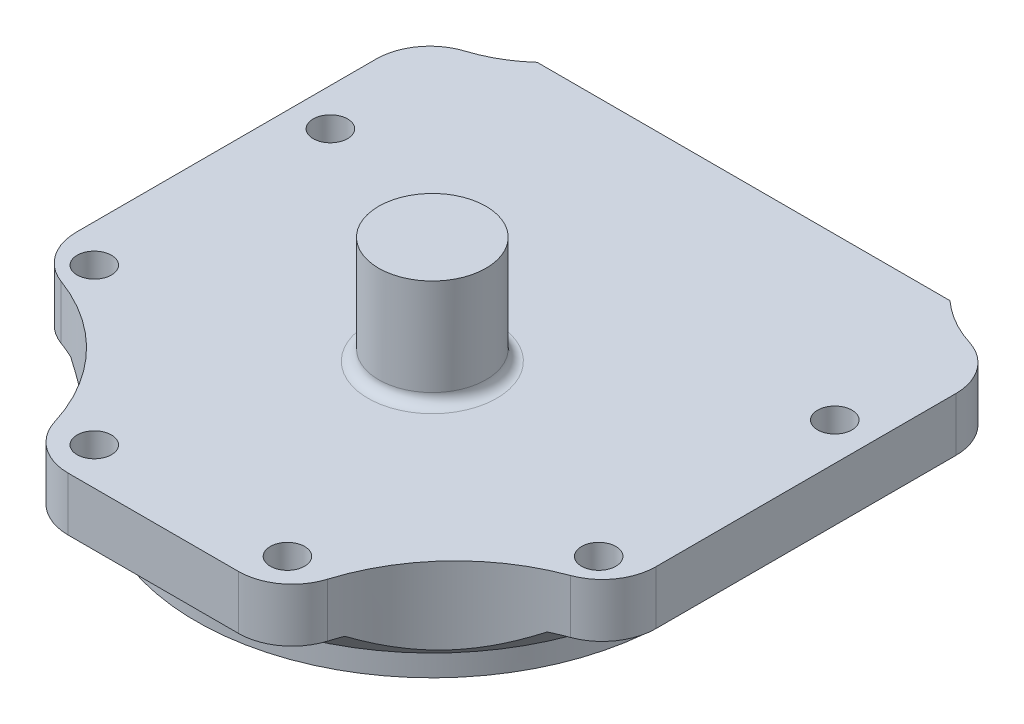
SolidWorks part; units mm, degrees
material "Резина"
ref_plane "Спереди" through (0, 0, 0) normal (0, 0, 1) x (1, 0, 0)
ref_plane "Сверху" through (0, 0, 0) normal (0, 1, 0) x (1, 0, 0)
ref_plane "Справа" through (0, 0, 0) normal (1, 0, 0) x (0, 0, -1)
ref_plane "Плоскость4" through (0, 0, 0) normal (0, -1, 0) x (-1, 0, 0)
sketch "Эскиз1" plane through (0, 0, 0) normal (0, -1, 0) x (-1, 0, 0)
  line L4 (11, -40.1669) -> (11, -12.2273)
  line L5 (3.2299, -5) -> (-35.2299, -5)
  line L6 (-43, -12.2273) -> (-43, -40.1669)
  line L7 (-23.9302, -60) -> (-8.0698, -60)
  line L8 (11, -40.1669) -> (11, -12.2273)
  line L9 (3.2299, -5) -> (-35.2299, -5)
  line L10 (-43, -12.2273) -> (-43, -40.1669)
  line L11 (-23.9302, -60) -> (-8.0698, -60)
  circle A0 centre (-39.5, -42) radius 1.6 construction
  circle A1 centre (-39.5, -20) radius 1.6 construction
  circle A3 centre (7.5, -42) radius 1.6 construction
  circle A4 centre (7.5, -20) radius 1.6 construction
  circle A5 centre (-39.5, -42) radius 1.6
  circle A6 centre (-39.5, -20) radius 1.6
  circle A7 centre (-25, -56.5) radius 1.6 construction
  circle A8 centre (7.5, -42) radius 1.6
  circle A9 centre (7.5, -20) radius 1.6
  arc A10 (11, -12.2273) -> (7.5094, -7.4605) centre (6, -12.2273) ccw
  arc A11 (3.2299, -5) -> (7.5094, -7.4605) centre (11, 3.5625) ccw
  arc A12 (-39.5094, -7.4605) -> (-35.2299, -5) centre (-43, 3.5625) ccw
  arc A13 (-39.5094, -7.4605) -> (-43, -12.2273) centre (-38, -12.2273) ccw
  arc A14 (-43, -40.1669) -> (-39.7203, -44.8616) centre (-38, -40.1669) ccw
  arc A15 (-28.7091, -56.4701) -> (-39.7203, -44.8616) centre (-45.9135, -61.7626) ccw
  arc A16 (-28.7091, -56.4701) -> (-23.9302, -60) centre (-23.9302, -55) ccw
  arc A17 (-8.0698, -60) -> (-3.2909, -56.4701) centre (-8.0698, -55) ccw
  arc A18 (7.7203, -44.8616) -> (-3.2909, -56.4701) centre (13.9135, -61.7626) ccw
  arc A19 (7.7203, -44.8616) -> (11, -40.1669) centre (6, -40.1669) ccw
  arc A20 (11, -12.2273) -> (7.5094, -7.4605) centre (6, -12.2273) ccw
  arc A21 (3.2299, -5) -> (7.5094, -7.4605) centre (11, 3.5625) ccw
  arc A22 (-39.5094, -7.4605) -> (-35.2299, -5) centre (-43, 3.5625) ccw
  arc A23 (-39.5094, -7.4605) -> (-43, -12.2273) centre (-38, -12.2273) ccw
  arc A24 (-43, -40.1669) -> (-39.7203, -44.8616) centre (-38, -40.1669) ccw
  arc A25 (-28.7091, -56.4701) -> (-39.7203, -44.8616) centre (-45.9135, -61.7626) ccw
  arc A26 (-28.7091, -56.4701) -> (-23.9302, -60) centre (-23.9302, -55) ccw
  arc A27 (-8.0698, -60) -> (-3.2909, -56.4701) centre (-8.0698, -55) ccw
  arc A28 (7.7203, -44.8616) -> (-3.2909, -56.4701) centre (13.9135, -61.7626) ccw
  arc A29 (7.7203, -44.8616) -> (11, -40.1669) centre (6, -40.1669) ccw
  circle A53 centre (-25, -56.5) radius 1.6
  circle A54 centre (-7, -56.5) radius 1.6 construction
  circle A55 centre (-7, -56.5) radius 1.6
  dimension "D1" = 0
extrude "Бобышка-Вытянуть1" add sketch "Эскиз1" along normal blind 5
sketch "Эскиз2" plane through (0, 0, 0) normal (0, 1, 0) x (1, 0, 0)
  circle A0 centre (16, -34) radius 5 construction
  circle A1 centre (16, -34) radius 5
extrude "Бобышка-Вытянуть2" add sketch "Эскиз2" along normal blind 10
fillet "Скругление1" radius 1 1 edges at (16, 0, 29)
sketch "Эскиз3" plane through (0, -5, 0) normal (0, -1, 0) x (1, 0, 0)
  circle A0 centre (16, 34) radius 5 construction
  circle A1 centre (16, 34) radius 5 construction
  circle A4 centre (16, 34) radius 22
  dimension "D2" = 44
extrude "Бобышка-Вытянуть3" add sketch "Эскиз3" along normal blind 5 contours A4
sketch "Эскиз4" plane through (0, -10, 0) normal (0, -1, 0) x (1, 0, 0)
  circle A0 centre (16, 34) radius 22 construction
  circle A1 centre (16, 34) radius 22 construction
  circle A2 centre (16, 34) radius 14
  circle A3 centre (16, 34) radius 19
  dimension "D1" = 28
  dimension "D2" = 38
extrude "Вырез-Вытянуть1" cut sketch "Эскиз4" against normal blind 7
sketch "Эскиз5" plane through (0, 0, 5) normal (0, 0, -1) x (-1, 0, 0)
  line L0 (-16, 0) -> (-16, -5) construction
  line L1 (3.2299, 0) -> (-35.2299, 0) construction
  line L2 (3.2299, -5) -> (-35.2299, -5) construction
ref_plane "Плоскость5" through (16, 0, 0) normal (1, 0, 0) x (0, -1, 0)
sketch "Эскиз6" plane through (16, 0, 0) normal (1, 0, 0) x (0, -1, 0)
  line L0 (3, -16) -> (10, -15)
  line L1 (10, -53) -> (10, -15) construction
  line L2 (10, -53) -> (10, -15) construction
  line L3 (10, -48) -> (10, -20) construction
  line L4 (10, -48) -> (10, -20) construction
  line L5 (10, -34) -> (3, -34) construction
  line L6 (3, -48) -> (3, -20) construction
  line L7 (3, -48) -> (3, -20) construction
  line L8 (3, -20) -> (3, -15) construction
  line L11 (3, -19) -> (10, -20)
  line L12 (10, -20) -> (3, -20)
  line L13 (3, -20) -> (3, -19)
  line L14 (10, -15) -> (3, -15)
  line L15 (3, -15) -> (3, -16)
  dimension "D1" = 15
  dimension "D2" = 18
revolve "Повернуть1" add sketch "Эскиз6" angle 360 about L5
chamfer "Фаска1" distance 3 angle 45 1 edges at (16, -5, 12)
